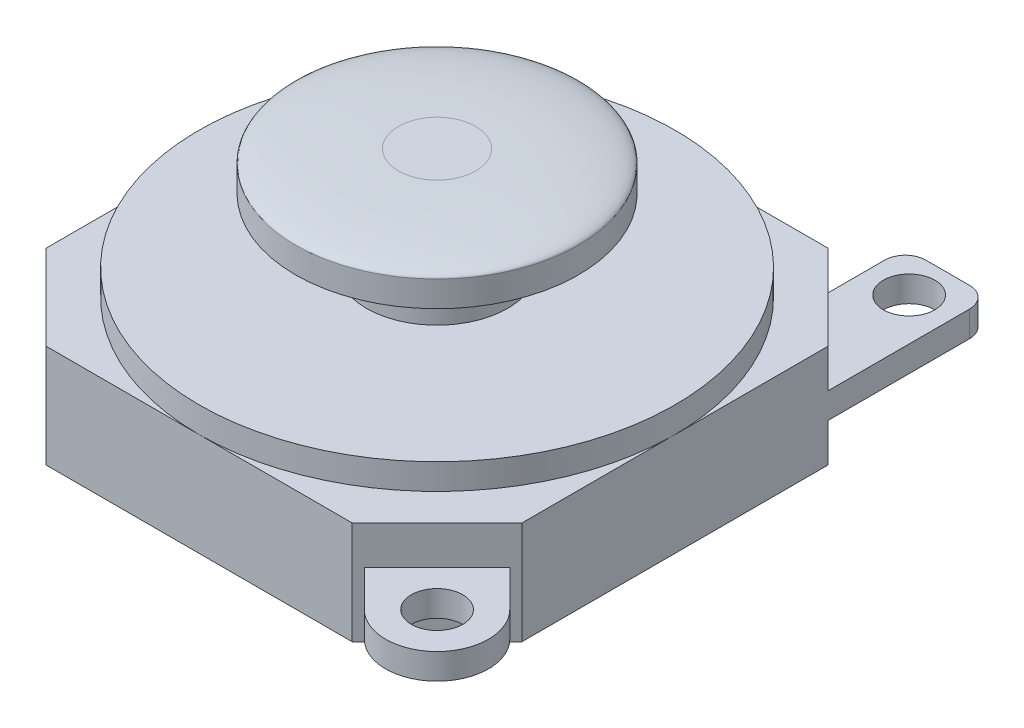
SolidWorks part; units mm, degrees
ref_plane "Front Plane" through (0, 0, 0) normal (0, 0, 1) x (1, 0, 0)
ref_plane "Top Plane" through (0, 0, 0) normal (0, 1, 0) x (1, 0, 0)
ref_plane "Right Plane" through (0, 0, 0) normal (1, 0, 0) x (0, 0, -1)
sketch "Sketch1" plane through (0, 0, 0) normal (0, 1, 0) x (1, 0, 0)
  line L0 (-5.9528, 9.25) -> (5.9528, 9.25)
  line L1 (5.9528, 9.25) -> (9.25, 5.9528)
  line L2 (9.25, 5.9528) -> (9.25, -5.9528)
  line L3 (9.25, -5.9528) -> (5.9528, -9.25)
  line L4 (5.9528, -9.25) -> (-5.9528, -9.25)
  line L5 (-5.9528, -9.25) -> (-9.25, -5.9528)
  line L6 (-9.25, -5.9528) -> (-9.25, 5.9528)
  line L7 (-9.25, 5.9528) -> (-5.9528, 9.25)
  line L8 (-9.25, 5.9528) -> (9.25, -5.9528) construction
  line L9 (9.25, 5.9528) -> (-9.25, -5.9528) construction
  point P2 (0, 0)
  dimension "D1" = 18.5
  dimension "D2" = 18.5
  dimension "D3" = 21.5
  dimension "D4" = 21.5
  dimension "D5" = 135
  dimension "D6" = 135
  dimension "D7" = 3.2972
  dimension "D8" = 3.2972
  dimension "D9" = 11.9056
  dimension "D10" = 11.9056
extrude "Boss-Extrude1" add sketch "Sketch1" along normal blind 4
sketch "Sketch2" plane through (0, 4, 0) normal (0, 1, 0) x (1, 0, 0)
  line L0 (9.25, -5.9528) -> (9.25, 5.9528) construction
  circle A0 centre (0, 0) radius 9.25
extrude "Boss-Extrude2" add sketch "Sketch2" along normal blind 1
ref_plane "Plane1" through (0, 1.5, 0) normal (0, 1, 0) x (1, 0, 0)
sketch "Sketch4" plane through (0, 1.5, 0) normal (0, 1, 0) x (1, 0, 0)
  line L0 (9.25, 5.9528) -> (9.25, 12.25)
  line L1 (5.9528, 9.25) -> (5.9528, 12.25)
  line L2 (5.9528, 12.25) -> (9.25, 12.25)
  line L3 (6.1872, -9.0156) -> (7.6014, -10.4298)
  line L4 (9.0156, -6.1872) -> (10.4298, -7.6014)
  line L5 (7.6014, -10.4298) -> (10.4298, -7.6014) construction
  line L6 (5.9528, -9.25) -> (6.1872, -9.0156) construction
  line L7 (-5.9528, -9.25) -> (5.9528, -9.25) construction
  line L9 (9.0156, -6.1872) -> (9.25, -5.9528) construction
  line L11 (5.9528, 9.25) -> (9.25, 9.25) construction
  line L12 (9.25, 9.25) -> (5.9528, 12.25) construction
  line L13 (9.25, 12.25) -> (5.9528, 9.25) construction
  line L14 (5.9528, 9.25) -> (9.25, 5.9528)
  line L15 (6.1872, -9.0156) -> (9.0156, -6.1872)
  circle A0 centre (7.6014, 10.75) radius 1
  circle A1 centre (9.0156, -9.0156) radius 1
  arc A2 (7.6014, -10.4298) -> (10.4298, -7.6014) centre (9.0156, -9.0156) ccw
  point P13 (10.4298, -10.4298)
  dimension "D4" = 2
  dimension "D5" = 2
  dimension "D1" = 4
  dimension "D3" = 21.5
  dimension "D6" = 4
extrude "Boss-Extrude3" add sketch "Sketch4" along normal blind 1
sketch "Sketch5" plane through (0, 5, 0) normal (0, 1, 0) x (1, 0, 0)
  circle A0 centre (0, 0) radius 2.75
  dimension "D1" = 5.5
extrude "Boss-Extrude4" add sketch "Sketch5" along normal blind 2.5
sketch "Sketch6" plane through (0, 7.5, 0) normal (0, 1, 0) x (1, 0, 0)
  circle A0 centre (0, 0) radius 5.5
  dimension "D1" = 11
extrude "Boss-Extrude5" add sketch "Sketch6" along normal blind 1.5
fillet "Fillet1" radius 0.5 1 edges at (0, 9, 5.5) second distance 4 first distance on face at (0, 9, 5.5)
fillet "Fillet2" radius 0.8 2 edges at (9.25, 2, -12.25) (5.9528, 2, -12.25)
sketch "Sketch7" plane through (0, 0, 0) normal (0, -1, 0) x (1, 0, 0)
  line L0 (-9.25, -5.9528) -> (-9.25, 5.9528) construction
  line L1 (-3.75, 8.75) -> (-2.25, 8.75)
  line L2 (-3.75, 8.75) -> (-3.75, 5.25)
  line L3 (-3.75, 5.25) -> (-2.25, 5.25)
  line L4 (-2.25, 8.75) -> (-2.25, 5.25)
  line L5 (-5.9528, 9.25) -> (5.9528, 9.25) construction
  line L6 (-1.75, 8.75) -> (-0.25, 8.75)
  line L7 (-1.75, 8.75) -> (-1.75, 5.25)
  line L8 (-1.75, 5.25) -> (-0.25, 5.25)
  line L9 (-0.25, 8.75) -> (-0.25, 5.25)
  line L10 (0.25, 8.75) -> (1.75, 8.75)
  line L11 (0.25, 8.75) -> (0.25, 5.25)
  line L12 (0.25, 5.25) -> (1.75, 5.25)
  line L13 (1.75, 8.75) -> (1.75, 5.25)
  line L14 (2.25, 8.75) -> (3.75, 8.75)
  line L15 (2.25, 8.75) -> (2.25, 5.25)
  line L16 (2.25, 5.25) -> (3.75, 5.25)
  line L17 (3.75, 8.75) -> (3.75, 5.25)
  line L19 (9.25, 5.9528) -> (9.25, -5.9528) construction
  dimension "D1" = 5.5
  dimension "D2" = 0.5
  dimension "D3" = 3.5
  dimension "D4" = 7
  dimension "D6" = 5.5
  dimension "D7" = 7.5
  dimension "D8" = 1.5
  dimension "D9" = 0.5
  dimension "D5" = 4
extrude "Boss-Extrude6" add sketch "Sketch7" along normal blind 0.1
